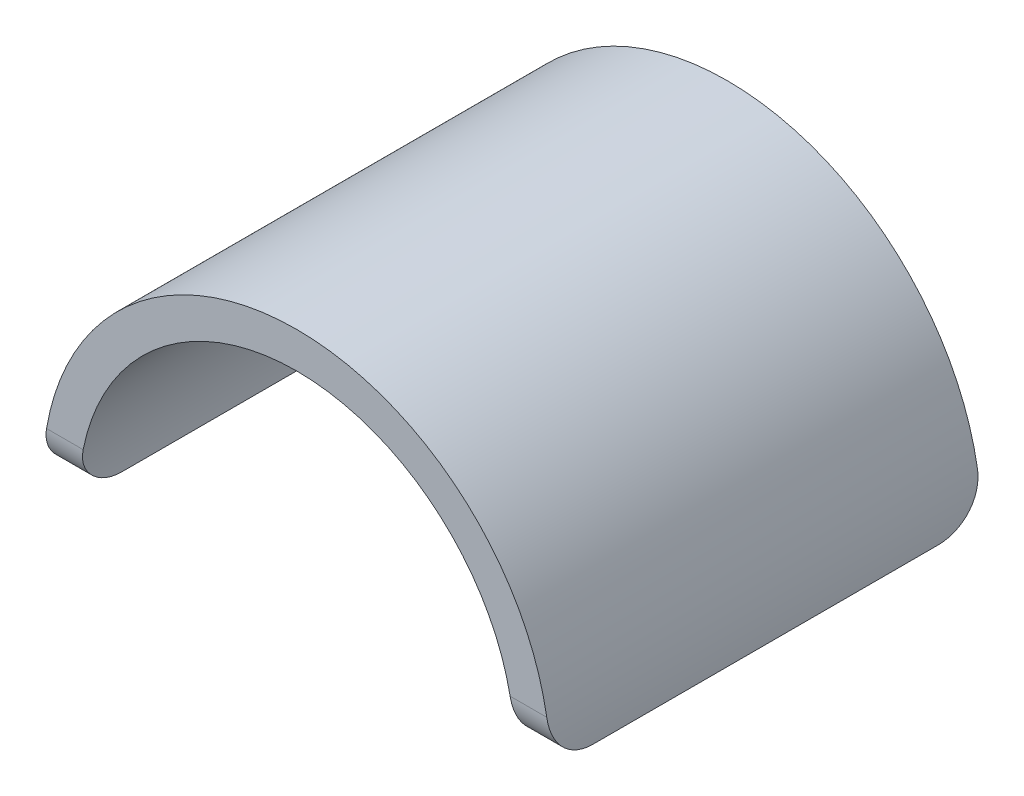
SolidWorks part; units mm, degrees
ref_plane "Piano frontale" through (0, 0, 0) normal (0, 0, 1) x (1, 0, 0)
ref_plane "Piano superiore" through (0, 0, 0) normal (0, 1, 0) x (1, 0, 0)
ref_plane "Piano destro" through (0, 0, 0) normal (1, 0, 0) x (0, 0, -1)
sketch "Schizzo1" plane through (0, 0, 0) normal (0, 0, 1) x (1, 0, 0)
  line L0 (-38.7303, 0) -> (42.7514, 0) construction
  line L3 (-29.628, 0) -> (-25.4242, 0)
  line L4 (25.4242, 0) -> (29.628, 0)
  arc A4 (25.4242, 0) -> (-25.4242, 0) centre (0, 0) ccw
  arc A5 (29.628, 0) -> (-29.628, 0) centre (0, 0) ccw
extrude "Estrusione-Estrusione2" add sketch "Schizzo1" along normal blind 50.2921
fillet "Raccordo1" radius 5 4 edges at (-27.5261, 0, 50.2921) (27.5261, 0, 50.2921) (-27.5261, 0, 0) (27.5261, 0, 0)
sketch "Schizzo9" plane through (0, 0, 0) normal (0, 0, -1) x (-1, 0, 0)
  line L0 (-24.9277, 5) -> (-29.2031, 5)
  line L1 (-29.2031, 5) -> (-24.9277, 5) construction
  line L2 (24.9277, 5) -> (29.2031, 5) construction
  line L3 (24.9277, 5) -> (29.2031, 5)
  arc A0 (-24.9277, 5) -> (24.9277, 5) centre (0, 0) cw
  arc A1 (-29.2031, 5) -> (29.2031, 5) centre (0, 0) cw
  point P8 (0, 27.5261)
  point P9 (-27.0654, 5)
  point P10 (27.0654, 5)
